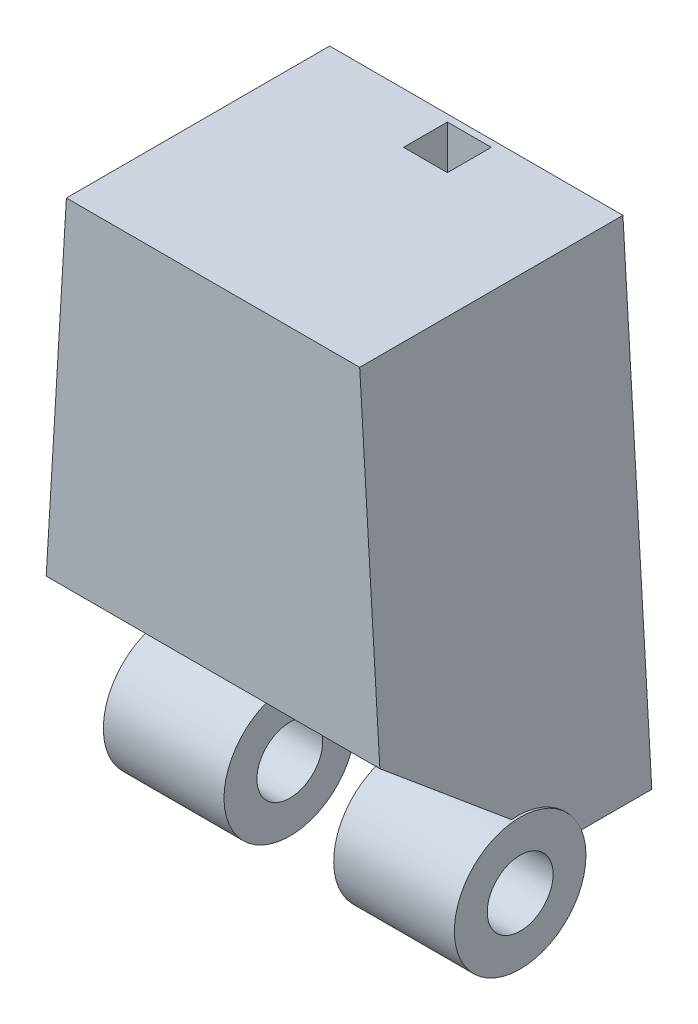
SolidWorks part; units mm, degrees
ref_plane "Front Plane" through (0, 0, 0) normal (0, 0, 1) x (1, 0, 0)
ref_plane "Top Plane" through (0, 0, 0) normal (0, 1, 0) x (1, 0, 0)
ref_plane "Right Plane" through (0, 0, 0) normal (1, 0, 0) x (0, 0, -1)
sketch "Sketch1" plane through (0, 0, 0) normal (0, 0, 1) x (1, 0, 0)
  line L0 (-56.5743, 0) -> (-40.5743, 0)
  line L2 (-56.5743, 0) -> (-55.2587, 22)
  line L3 (-40.5743, 0) -> (-41.8899, 22)
  arc A0 (-41.8899, 22) -> (-55.2587, 22) centre (-48.5743, 22) ccw
extrude "Boss-Extrude1" add sketch "Sketch1" along normal blind 12
sketch "Sketch2" plane through (0, 0, 12) normal (0, 0, 1) x (1, 0, 0)
  line L0 (-40.5743, 0) -> (-56.5743, 0)
  line L1 (-48.5743, 0) -> (-48.5743, 29.5391)
ref_plane "Plane1" through (-48.5743, 0, 0) normal (1, 0, 0) x (0, 0, -1)
sketch "Sketch3" plane through (-48.5743, 0, 0) normal (1, 0, 0) x (0, 0, -1)
  line L0 (0, 0) -> (-4, 0)
  line L1 (-12, 0) -> (0, 0) construction
  line L2 (-4, 0) -> (-12, 6.614)
  line L3 (-12, 0) -> (-12, 22) construction
  line L4 (-12, 6.614) -> (-12, 0)
  line L5 (-12, 0) -> (-4, 0)
extrude "Cut-Extrude1" cut sketch "Sketch3" against normal through all both and the other way through all contours L4 L5 L2 region at (-48.5743, 2.2047, 9.3333)
sketch "Sketch6" plane through (-48.5743, 0, 0) normal (1, 0, 0) x (0, 0, -1)
  line L1 (0, 0) -> (-12, 0)
  line L2 (-6, 0) -> (-6, -1.1)
  circle A0 centre (-6, -1.1) radius 1.5
  circle A1 centre (-6, -1.1) radius 3
extrude "Boss-Extrude2" add sketch "Sketch6" along normal mid plane 16 contours L1 A1 A0 | L1 A1 A0 region at (-48.5743, -0.5537, 3.1241) region at (-48.5743, 0.8343, 6)
extrude "Cut-Extrude2" cut sketch "Sketch6<3>" against normal mid plane 5 contours L1 A1 A0 | L1 A1 A0 region at (-48.5743, -0.5537, 3.1241) region at (-48.5743, 0.8343, 6)
sketch "Sketch6<3>" plane through (-48.5743, 0, 0) normal (1, 0, 0) x (0, 0, -1) same geometry as "Sketch6"
sketch "Sketch7" plane through (-48.5743, 0, 0) normal (1, 0, 0) x (0, 0, -1)
  line L0 (-7.1617, 2.6139) -> (-11.0152, 5.7998)
  line L1 (-6.2821, 1.8867) -> (-12, 6.614) construction
  line L2 (-7.1617, 2.6139) -> (-3.9757, 6.4674)
  line L3 (-3.9757, 6.4674) -> (-7.8293, 9.6534)
  line L4 (-7.8293, 9.6534) -> (-11.0152, 5.7998)
  line L5 (-12, 6.614) -> (-6.2821, 1.8867) construction
extrude "Cut-Extrude3" cut sketch "Sketch7" against normal mid plane 10
sketch "Sketch8" plane through (-48.5743, 0, 0) normal (1, 0, 0) x (0, 0, -1)
  circle A0 centre (-7.5481, 6.1771) radius 1.5
extrude "Boss-Extrude3" add sketch "Sketch8" along normal mid plane 11
sketch "Sketch9" plane through (-48.5743, 0, 0) normal (1, 0, 0) x (0, 0, -1)
  line L1 (-12, 28.6844) -> (0, 28.6844)
  line L2 (-12, 28.6844) -> (-12, 22)
  line L3 (-12, 22) -> (0, 22)
  line L4 (0, 28.6844) -> (0, 22)
extrude "Cut-Extrude4" cut sketch "Sketch9" against normal through all both and the other way through all
sketch "Sketch10" plane through (-48.5743, 0, 0) normal (1, 0, 0) x (0, 0, -1)
  line L0 (-2.3161, 0) -> (-0.3161, 0)
  line L1 (-3.2089, 0) -> (0, 0) construction
  line L2 (-0.3161, 0) -> (-0.3161, 23.3351)
  line L3 (-0.3161, 23.3351) -> (-2.3161, 23.3351)
  line L4 (-2.3161, 23.3351) -> (-2.3161, 0)
  point P5 (-1.3161, 0)
extrude "Cut-Extrude5" cut sketch "Sketch10" against normal mid plane 2
